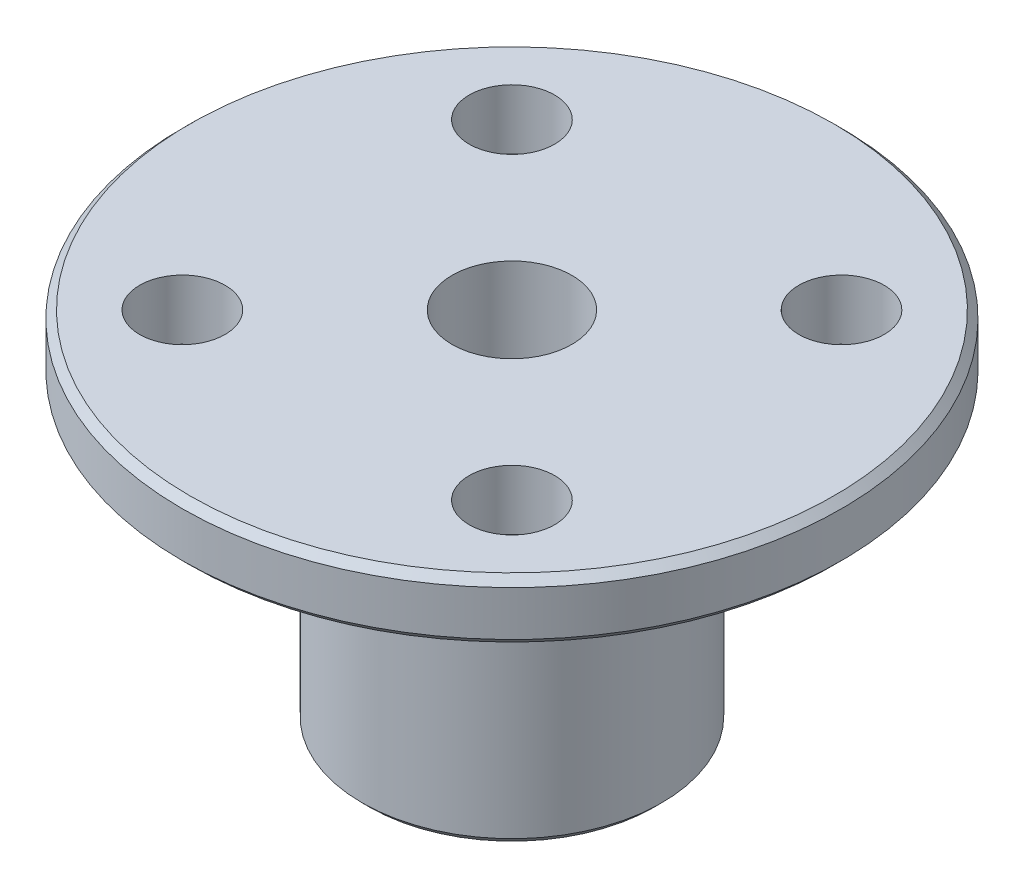
SolidWorks part; units mm, degrees
ref_plane "Front Plane" through (0, 0, 0) normal (0, 0, 1) x (1, 0, 0)
ref_plane "Top Plane" through (0, 0, 0) normal (0, 1, 0) x (1, 0, 0)
ref_plane "Right Plane" through (0, 0, 0) normal (1, 0, 0) x (0, 0, -1)
ref_axis "X" through (-88.99, 0, 0) along (1, 0, 0)
ref_axis "Y" through (0, 55, 0) along (0, -1, 0)
ref_axis "Z" through (0, 0, -88.99) along (0, 0, 1)
sketch "Sketch1" plane through (0, 0, 0) normal (0, 1, 0) x (1, 0, 0)
  line L1 (-5.5, 5.5) -> (5.5, 5.5)
  line L2 (-5.5, 5.5) -> (-5.5, -5.5)
  line L3 (-5.5, -5.5) -> (5.5, -5.5)
  line L4 (5.5, 5.5) -> (5.5, -5.5)
  line L5 (-5.5, 5.5) -> (5.5, -5.5) construction
  line L6 (-5.5, -5.5) -> (5.5, 5.5) construction
  circle A0 centre (0, 0) radius 11
  circle A1 centre (0, 0) radius 2
  circle A2 centre (0, 0) radius 5
  circle A3 centre (-5.5, 5.5) radius 1.425
  circle A4 centre (5.5, 5.5) radius 1.425
  circle A5 centre (5.5, -5.5) radius 1.425
  circle A6 centre (-5.5, -5.5) radius 1.425
  dimension "D1" = 22
  dimension "D2" = 4
  dimension "D3" = 10
  dimension "D5" = 2.85
  dimension "D4" = 11
extrude "Boss-Extrude1" add sketch "Sketch1" against normal blind 2 contours A0 A6 L2 A3 L1 A4 L4 A5 L3 | A6 L3 A5 L4 A4 L1 A3 L2 A2 | A2 A1 region at (0, 0, -5.3444) region at (-10.6889, 0, 0) region at (-4.8586, 0, 0)
extrude "Boss-Extrude2" add sketch "Sketch1<3>" against normal blind 12 contours A2 A1 region at (-4.8586, 0, 0)
sketch "Sketch1<3>" plane through (0, 0, 0) normal (0, 1, 0) x (1, 0, 0) same geometry as "Sketch1"
chamfer "Chamfer1" distance 0.25 angle 45 5 edges at (0, -12, 2) (0, -2, 5) (0, -12, 5) (0, -2, 11) (0, 0, 11)
